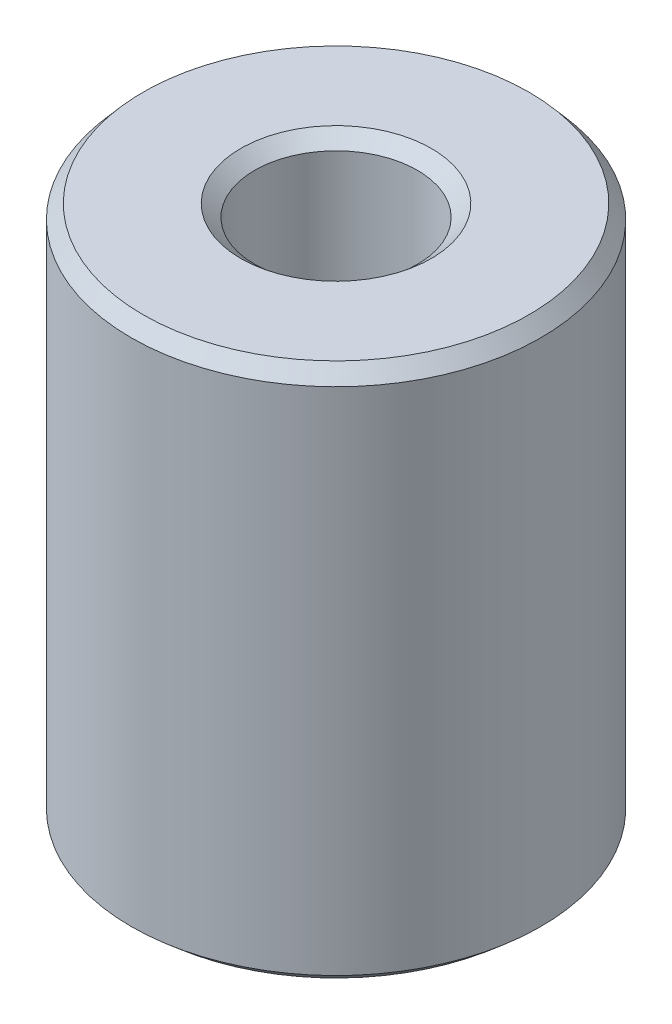
SolidWorks part; units mm, degrees
ref_plane "Front Plane" through (0, 0, 0) normal (0, 0, 1) x (1, 0, 0)
ref_plane "Top Plane" through (0, 0, 0) normal (0, 1, 0) x (1, 0, 0)
ref_plane "Right Plane" through (0, 0, 0) normal (1, 0, 0) x (0, 0, -1)
sketch "Sketch1" plane through (0, 0, 0) normal (0, 1, 0) x (1, 0, 0)
  circle A0 centre (0, 0) radius 27.5
  dimension "SLEEVE_OD" = 55
extrude "Boss-Extrude1" add sketch "Sketch1" along normal blind 71.935
sketch "Sketch2" plane through (0, 0, 0) normal (0, 1, 0) x (1, 0, 0)
  circle A0 centre (0, 0) radius 10.931
  dimension "BORE_D" = 21.8619
extrude "Cut-Extrude1" cut sketch "Sketch2" along normal through all
chamfer "Chamfer1" distance 1.8695 angle 40.679 4 edges at (0, 71.935, 10.931) (0, 0, 10.931) (0, 0, 27.5) (0, 71.935, 27.5) first distance on face at (0, 71.935, 10.931) first distance on face at (0, 0, 10.931) first distance on face at (0, 71.935, 27.5)
